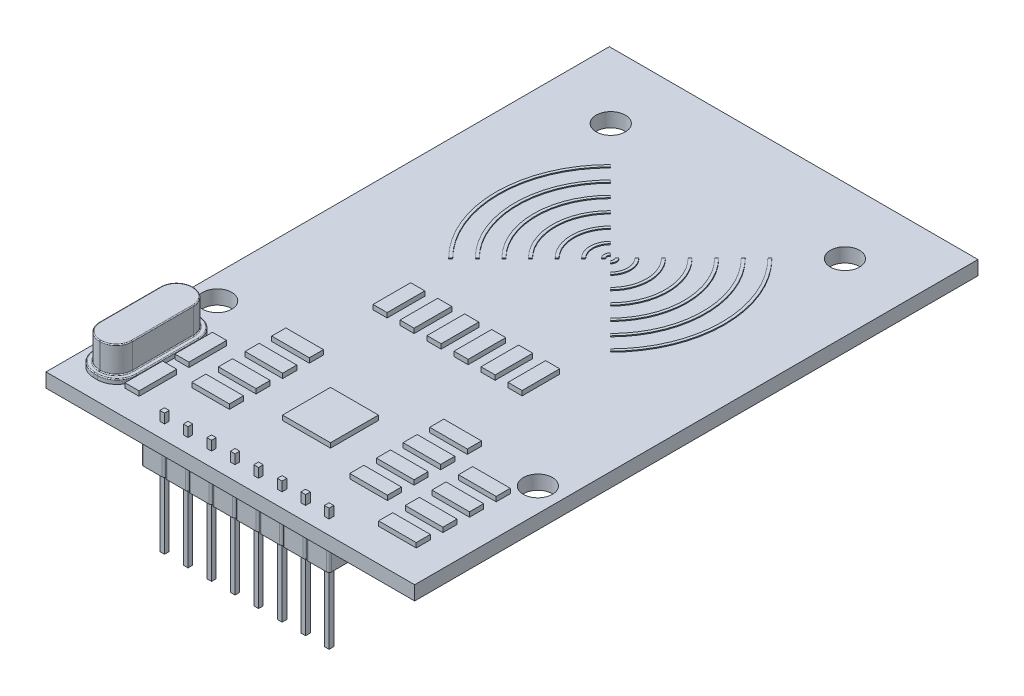
SolidWorks part; units mm, degrees
ref_plane "Front Plane" through (0, 0, 0) normal (0, 0, 1) x (1, 0, 0)
ref_plane "Top Plane" through (0, 0, 0) normal (0, 1, 0) x (1, 0, 0)
ref_plane "Right Plane" through (0, 0, 0) normal (1, 0, 0) x (0, 0, -1)
sketch "Sketch1" plane through (0, 0, 0) normal (0, 1, 0) x (1, 0, 0)
  line L1 (-19.6, 29.95) -> (19.6, 29.95)
  line L2 (-19.6, 29.95) -> (-19.6, -29.95)
  line L3 (-19.6, -29.95) -> (19.6, -29.95)
  line L4 (19.6, 29.95) -> (19.6, -29.95)
  line L5 (-19.6, 29.95) -> (19.6, -29.95) construction
  line L6 (-19.6, -29.95) -> (19.6, 29.95) construction
  point P0 (0, 0)
  dimension "D1" = 39.2
  dimension "D2" = 59.9
extrude "Boss-Extrude1" add sketch "Sketch1" along normal blind 1.5
sketch "Sketch3" plane through (0, 1.5, 0) normal (0, 1, 0) x (1, 0, 0)
  line L0 (0, 29.95) -> (0, -29.95) construction
  line L2 (19.6, 29.95) -> (-19.6, 29.95) construction
  line L3 (-17.05, -14.3) -> (17.05, -14.3) construction
  line L4 (-12.45, 22.95) -> (12.45, 22.95) construction
  line L5 (-19.6, -29.95) -> (19.6, -29.95) construction
  circle A0 centre (12.45, 22.95) radius 1.55
  circle A1 centre (-12.45, 22.95) radius 1.55
  circle A2 centre (17.05, -14.3) radius 1.55
  circle A3 centre (-17.05, -14.3) radius 1.55
  point P16 (0, 22.95)
  point P17 (0, -14.3)
  dimension "D1" = 3.1
  dimension "D2" = 12.45
  dimension "D3" = 7
  dimension "D6" = 17.05
  dimension "D7" = 15.65
extrude "Cut-Extrude1" cut sketch "Sketch3" against normal up to surface (1.5 mm away) up to face at (0, 0, 0)
sketch "Sketch4" plane through (0, 1.5, 0) normal (0, 1, 0) x (1, 0, 0)
  line L0 (-19.6, -29.95) -> (19.6, -29.95) construction
  line L1 (-9.75, -26.95) -> (-7.75, -26.95)
  line L2 (-10, -27.2) -> (-10, -29.2)
  line L3 (-9.75, -29.45) -> (-7.75, -29.45)
  line L5 (-19.6, 29.95) -> (-19.6, -29.95) construction
  line L7 (-7.25, -29.45) -> (-5.25, -29.45)
  line L9 (-7.25, -26.95) -> (-5.25, -26.95)
  line L11 (-4.75, -29.45) -> (-2.75, -29.45)
  line L13 (-4.75, -26.95) -> (-2.75, -26.95)
  line L15 (-2.25, -29.45) -> (-0.25, -29.45)
  line L17 (-2.25, -26.95) -> (-0.25, -26.95)
  line L19 (0.25, -29.45) -> (2.25, -29.45)
  line L21 (0.25, -26.95) -> (2.25, -26.95)
  line L23 (2.75, -29.45) -> (4.75, -29.45)
  line L25 (2.75, -26.95) -> (4.75, -26.95)
  line L27 (5.25, -29.45) -> (7.25, -29.45)
  line L29 (5.25, -26.95) -> (7.25, -26.95)
  line L30 (10, -27.2) -> (10, -29.2)
  line L31 (7.75, -29.45) -> (9.75, -29.45)
  line L33 (7.75, -26.95) -> (9.75, -26.95)
  line L34 (-7.5, -27.2) -> (-7.5, -29.2) [skipped]
  line L35 (-5, -27.2) -> (-5, -29.2) [skipped]
  line L36 (-2.5, -27.2) -> (-2.5, -29.2) [skipped]
  line L37 (0, -27.2) -> (0, -29.2) [skipped]
  line L38 (2.5, -27.2) -> (2.5, -29.2) [skipped]
  line L39 (5, -27.2) -> (5, -29.2) [skipped]
  line L40 (7.5, -27.2) -> (7.5, -29.2) [skipped]
  arc A1 (-7.75, -26.95) -> (-7.5, -27.2) centre (-7.75, -27.2) cw
  arc A2 (-7.5, -29.2) -> (-7.75, -29.45) centre (-7.75, -29.2) cw
  arc A3 (-9.75, -29.45) -> (-10, -29.2) centre (-9.75, -29.2) cw
  arc A4 (-10, -27.2) -> (-9.75, -26.95) centre (-9.75, -27.2) cw
  arc A5 (-5, -29.2) -> (-5.25, -29.45) centre (-5.25, -29.2) cw
  arc A6 (-7.25, -29.45) -> (-7.5, -29.2) centre (-7.25, -29.2) cw
  arc A7 (-7.5, -27.2) -> (-7.25, -26.95) centre (-7.25, -27.2) cw
  arc A8 (-5.25, -26.95) -> (-5, -27.2) centre (-5.25, -27.2) cw
  arc A10 (-2.5, -29.2) -> (-2.75, -29.45) centre (-2.75, -29.2) cw
  arc A11 (-4.75, -29.45) -> (-5, -29.2) centre (-4.75, -29.2) cw
  arc A12 (-5, -27.2) -> (-4.75, -26.95) centre (-4.75, -27.2) cw
  arc A13 (-2.75, -26.95) -> (-2.5, -27.2) centre (-2.75, -27.2) cw
  arc A15 (0, -29.2) -> (-0.25, -29.45) centre (-0.25, -29.2) cw
  arc A16 (-2.25, -29.45) -> (-2.5, -29.2) centre (-2.25, -29.2) cw
  arc A17 (-2.5, -27.2) -> (-2.25, -26.95) centre (-2.25, -27.2) cw
  arc A18 (-0.25, -26.95) -> (0, -27.2) centre (-0.25, -27.2) cw
  arc A20 (2.5, -29.2) -> (2.25, -29.45) centre (2.25, -29.2) cw
  arc A21 (0.25, -29.45) -> (0, -29.2) centre (0.25, -29.2) cw
  arc A22 (0, -27.2) -> (0.25, -26.95) centre (0.25, -27.2) cw
  arc A23 (2.25, -26.95) -> (2.5, -27.2) centre (2.25, -27.2) cw
  arc A25 (5, -29.2) -> (4.75, -29.45) centre (4.75, -29.2) cw
  arc A26 (2.75, -29.45) -> (2.5, -29.2) centre (2.75, -29.2) cw
  arc A27 (2.5, -27.2) -> (2.75, -26.95) centre (2.75, -27.2) cw
  arc A28 (4.75, -26.95) -> (5, -27.2) centre (4.75, -27.2) cw
  arc A30 (7.5, -29.2) -> (7.25, -29.45) centre (7.25, -29.2) cw
  arc A31 (5.25, -29.45) -> (5, -29.2) centre (5.25, -29.2) cw
  arc A32 (5, -27.2) -> (5.25, -26.95) centre (5.25, -27.2) cw
  arc A33 (7.25, -26.95) -> (7.5, -27.2) centre (7.25, -27.2) cw
  arc A35 (10, -29.2) -> (9.75, -29.45) centre (9.75, -29.2) cw
  arc A36 (7.75, -29.45) -> (7.5, -29.2) centre (7.75, -29.2) cw
  arc A37 (7.5, -27.2) -> (7.75, -26.95) centre (7.75, -27.2) cw
  arc A38 (9.75, -26.95) -> (10, -27.2) centre (9.75, -27.2) cw
  point P12 (-7.5, -26.95)
  point P17 (-10, -29.45)
  point P20 (-10, -26.95)
  dimension "D7" = 0.25
  dimension "D1" = 2.5
  dimension "D2" = 2.5
  dimension "D3" = 0.5
  dimension "D4" = 9.6
  dimension "D8" = 8
extrude "Boss-Extrude3" add sketch "Sketch4" against normal blind 4
ref_plane "Plane1" through (0, -1, 0) normal (0, -1, 0) x (-1, 0, 0)
sketch "Sketch8" plane through (0, 1.5, 0) normal (0, 1, 0) x (1, 0, 0)
  line L0 (-19.6, -29.95) -> (19.6, -29.95) construction
  line L1 (-16.5, -17.15) -> (-16.15, -17.15)
  line L2 (-18.6, -19.25) -> (-18.6, -25.85)
  line L3 (-16.5, -27.95) -> (-16.15, -27.95)
  line L4 (-14.05, -19.25) -> (-14.05, -25.85)
  line L6 (-19.6, 29.95) -> (-19.6, -29.95) construction
  arc A0 (-18.6, -25.85) -> (-16.5, -27.95) centre (-16.5, -25.85) ccw
  arc A1 (-16.15, -27.95) -> (-14.05, -25.85) centre (-16.15, -25.85) ccw
  arc A2 (-16.15, -17.15) -> (-14.05, -19.25) centre (-16.15, -19.25) cw
  arc A3 (-16.5, -17.15) -> (-18.6, -19.25) centre (-16.5, -19.25) ccw
  point P6 (-18.6, -27.95)
  point P11 (-14.05, -17.15)
  point P14 (-18.6, -17.15)
  dimension "D3" = 2.1
  dimension "D1" = 10.8
  dimension "D2" = 4.55
  dimension "D4" = 1
  dimension "D5" = 2
extrude "Boss-Extrude4" add sketch "Sketch8" along normal blind 0.5
sketch "Sketch10" plane through (0, 2, 0) normal (0, 1, 0) x (1, 0, 0)
  line L0 (-16.325, -17.15) -> (-16.325, -27.95) construction
  line L1 (-16.15, -17.15) -> (-16.5, -17.15) construction
  line L2 (-16.5, -27.95) -> (-16.15, -27.95) construction
  line L3 (-18.6, -22.55) -> (-14.05, -22.55) construction
  line L4 (-18.6, -19.25) -> (-18.6, -25.85) construction
  line L5 (-14.05, -25.85) -> (-14.05, -19.25) construction
  line L7 (-16.375, -17.6) -> (-16.275, -17.6)
  line L8 (-18.075, -19.3) -> (-18.075, -25.8)
  line L9 (-16.375, -27.5) -> (-16.275, -27.5)
  line L10 (-14.575, -19.3) -> (-14.575, -25.8)
  line L11 (-18.075, -17.6) -> (-14.575, -27.5) construction
  line L12 (-18.075, -27.5) -> (-14.575, -17.6) construction
  arc A0 (-18.075, -25.8) -> (-16.375, -27.5) centre (-16.375, -25.8) ccw
  arc A1 (-16.275, -27.5) -> (-14.575, -25.8) centre (-16.275, -25.8) ccw
  arc A2 (-14.575, -19.3) -> (-16.275, -17.6) centre (-16.275, -19.3) ccw
  arc A3 (-16.375, -17.6) -> (-18.075, -19.3) centre (-16.375, -19.3) ccw
  point P12 (-16.325, -22.55)
  dimension "D3" = 1.7
  dimension "D1" = 3.5
  dimension "D2" = 9.9
extrude "Boss-Extrude5" add sketch "Sketch10" along normal blind 2.8
fillet "Fillet1" radius 0.1 24 edges at (-17.5771, 4.8, 18.0979) (-16.325, 4.8, 17.6) (-15.0729, 4.8, 18.0979) (-14.575, 4.8, 22.55) (-15.0729, 4.8, 27.0021) (-16.325, 4.8, 27.5) (-17.5771, 4.8, 27.0021) (-17.5771, 2, 18.0979) (-16.325, 2, 17.6) (-15.0729, 2, 18.0979) (-14.575, 2, 22.55) (-15.0729, 2, 27.0021) (-16.325, 2, 27.5) (-17.5771, 2, 27.0021) (-17.9849, 2, 17.7651) (-16.325, 2, 17.15) (-14.6651, 2, 17.7651) (-14.05, 2, 22.55) (-14.6651, 2, 27.3349) (-16.325, 2, 27.95) (-17.9849, 2, 27.3349) (-18.075, 4.8, 22.55) (-18.075, 2, 22.55) (-18.6, 2, 22.55)
sketch "Sketch11" plane through (0, 1.5, 0) normal (0, 1, 0) x (1, 0, 0)
  line L0 (-0.2475, 10.6975) -> (-0.4596, 10.9096)
  line L1 (-0.35, 10.45) -> (-19.6, 10.45) construction
  line L2 (-19.6, 29.95) -> (-19.6, -29.95) construction
  line L3 (19.6, 29.95) -> (-19.6, 29.95) construction
  line L4 (0.2475, 10.6975) -> (0.4596, 10.9096)
  line L5 (-0.2475, 10.2025) -> (-0.4596, 9.9904)
  line L6 (0.2475, 10.2025) -> (0.4596, 9.9904)
  line L7 (-8.4853, 18.9353) -> (-8.5913, 19.0413)
  line L8 (-8.5913, 1.8587) -> (-8.4853, 1.9647)
  line L9 (8.4853, 1.9647) -> (8.5913, 1.8587)
  line L10 (8.4853, 18.9353) -> (8.5913, 19.0413)
  line L11 (-8.3792, 18.8292) -> (-8.4853, 18.9353)
  line L12 (-6.965, 17.415) -> (-7.1771, 17.6271)
  line L13 (-5.5508, 16.0008) -> (-5.7629, 16.2129)
  line L14 (-4.1366, 14.5866) -> (-4.3487, 14.7987)
  line L15 (-2.7224, 13.1724) -> (-2.9345, 13.3845)
  line L16 (-1.3081, 11.7581) -> (-1.5203, 11.9703)
  line L17 (-1.3081, 9.1419) -> (-1.5203, 8.9297)
  line L18 (-2.7224, 7.7276) -> (-2.9345, 7.5155)
  line L19 (-4.1366, 6.3134) -> (-4.3487, 6.1013)
  line L20 (-5.5508, 4.8992) -> (-5.7629, 4.6871)
  line L21 (-8.3792, 2.0708) -> (-8.4853, 1.9647)
  line L22 (1.3081, 9.1419) -> (1.5203, 8.9297)
  line L23 (2.7224, 7.7276) -> (2.9345, 7.5155)
  line L24 (4.1366, 6.3134) -> (4.3487, 6.1013)
  line L25 (5.5508, 4.8992) -> (5.7629, 4.6871)
  line L26 (6.965, 3.485) -> (7.1771, 3.2729)
  line L27 (8.3792, 2.0708) -> (8.4853, 1.9647)
  line L28 (1.3081, 11.7581) -> (1.5203, 11.9703)
  line L29 (2.7224, 13.1724) -> (2.9345, 13.3845)
  line L30 (4.1366, 14.5866) -> (4.3487, 14.7987)
  line L31 (5.5508, 16.0008) -> (5.7629, 16.2129)
  line L32 (6.965, 17.415) -> (7.1771, 17.6271)
  line L33 (8.3792, 18.8292) -> (8.4853, 18.9353)
  line L34 (-6.965, 3.485) -> (-7.1771, 3.2729)
  line L35 (0, 10.45) -> (0, 29.95) construction
  arc A0 (-0.3536, 10.8036) -> (-0.3536, 10.0964) centre (0, 10.45) ccw construction
  arc A1 (-1.4142, 11.8642) -> (-1.4142, 9.0358) centre (0, 10.45) ccw construction
  arc A2 (-2.8284, 13.2784) -> (-2.8284, 7.6216) centre (0, 10.45) ccw construction
  arc A3 (-4.2426, 14.6926) -> (-4.2426, 6.2074) centre (0, 10.45) ccw construction
  arc A4 (-5.6569, 16.1069) -> (-5.6569, 4.7931) centre (0, 10.45) ccw construction
  arc A5 (-5.6569, 16.1069) -> (-5.6569, 4.7931) centre (0, 10.45) ccw
  arc A6 (-7.0711, 17.5211) -> (-7.0711, 3.3789) centre (0, 10.45) ccw construction
  arc A7 (-8.4853, 18.9353) -> (-8.4853, 1.9647) centre (0, 10.45) ccw construction
  arc A8 (0.3536, 10.0964) -> (0.3536, 10.8036) centre (0, 10.45) ccw construction
  arc A9 (1.4142, 9.0358) -> (1.4142, 11.8642) centre (0, 10.45) ccw construction
  arc A10 (2.8284, 7.6216) -> (2.8284, 13.2784) centre (0, 10.45) ccw construction
  arc A11 (4.2426, 6.2074) -> (4.2426, 14.6926) centre (0, 10.45) ccw construction
  arc A12 (5.6569, 4.7931) -> (5.6569, 16.1069) centre (0, 10.45) ccw construction
  arc A13 (5.6569, 4.7931) -> (5.6569, 16.1069) centre (0, 10.45) ccw
  arc A14 (7.0711, 3.3789) -> (7.0711, 17.5211) centre (0, 10.45) ccw construction
  arc A15 (8.4853, 1.9647) -> (8.4853, 18.9353) centre (0, 10.45) ccw construction
  arc A16 (-8.5913, 19.0413) -> (-8.5913, 1.8587) centre (0, 10.45) ccw
  arc A17 (-7.1771, 17.6271) -> (-7.1771, 3.2729) centre (0, 10.45) ccw
  arc A18 (-5.7629, 16.2129) -> (-5.7629, 4.6871) centre (0, 10.45) ccw
  arc A19 (-4.3487, 14.7987) -> (-4.3487, 6.1013) centre (0, 10.45) ccw
  arc A20 (-2.9345, 13.3845) -> (-2.9345, 7.5155) centre (0, 10.45) ccw
  arc A21 (-1.5203, 11.9703) -> (-1.5203, 8.9297) centre (0, 10.45) ccw
  arc A22 (-0.4596, 10.9096) -> (-0.4596, 9.9904) centre (0, 10.45) ccw
  arc A23 (0.4596, 9.9904) -> (0.4596, 10.9096) centre (0, 10.45) ccw
  arc A24 (1.5203, 8.9297) -> (1.5203, 11.9703) centre (0, 10.45) ccw
  arc A25 (2.9345, 7.5155) -> (2.9345, 13.3845) centre (0, 10.45) ccw
  arc A26 (4.3487, 6.1013) -> (4.3487, 14.7987) centre (0, 10.45) ccw
  arc A27 (5.7629, 4.6871) -> (5.7629, 16.2129) centre (0, 10.45) ccw
  arc A28 (7.1771, 3.2729) -> (7.1771, 17.6271) centre (0, 10.45) ccw
  arc A29 (8.5913, 1.8587) -> (8.5913, 19.0413) centre (0, 10.45) ccw
  arc A30 (-8.3792, 18.8292) -> (-8.3792, 2.0708) centre (0, 10.45) ccw
  arc A31 (-6.965, 17.415) -> (-6.965, 3.485) centre (0, 10.45) ccw
  arc A32 (-5.5508, 16.0008) -> (-5.5508, 4.8992) centre (0, 10.45) ccw
  arc A33 (-4.1366, 14.5866) -> (-4.1366, 6.3134) centre (0, 10.45) ccw
  arc A34 (-2.7224, 13.1724) -> (-2.7224, 7.7276) centre (0, 10.45) ccw
  arc A35 (-1.3081, 11.7581) -> (-1.3081, 9.1419) centre (0, 10.45) ccw
  arc A36 (-0.2475, 10.6975) -> (-0.2475, 10.2025) centre (0, 10.45) ccw
  arc A37 (0.2475, 10.2025) -> (0.2475, 10.6975) centre (0, 10.45) ccw
  arc A38 (1.3081, 9.1419) -> (1.3081, 11.7581) centre (0, 10.45) ccw
  arc A39 (2.7224, 7.7276) -> (2.7224, 13.1724) centre (0, 10.45) ccw
  arc A40 (4.1366, 6.3134) -> (4.1366, 14.5866) centre (0, 10.45) ccw
  arc A41 (5.5508, 4.8992) -> (5.5508, 16.0008) centre (0, 10.45) ccw
  arc A42 (6.965, 3.485) -> (6.965, 17.415) centre (0, 10.45) ccw
  arc A43 (8.3792, 2.0708) -> (8.3792, 18.8292) centre (0, 10.45) ccw
  dimension "D1" = 45
  dimension "D2" = 0.5
  dimension "D3" = 2
  dimension "D4" = 6
  dimension "D5" = 10
  dimension "D6" = 19.5
  dimension "D10" = 8
  dimension "D11" = 4
  dimension "D12" = 12
  dimension "D7" = 45
  dimension "D8" = 45
  dimension "D9" = 45
  dimension "D13" = 0.15
  dimension "D14" = 0.15
extrude "Boss-Extrude6" add sketch "Sketch11" along normal blind 0.1 contours A16 L8 L21 A30 L11 L7 | A17 L34 A31 L12 | A18 L20 A32 L13 | A19 L19 A33 L14 | A20 L18 A34 L15 | A35 L17 A21 L16 | A36 L5 A22 L0 | A23 L4 A37 L6 | A24 L28 A38 L22 | A25 L29 A39 L23 | A26 L30 A40 L24 | A27 L31 A41 L25 | A28 L32 A42 L26 | A29 L10 L33 A43 L27 L9
sketch "Esboço1" plane through (0, 1.5, 0) normal (0, 1, 0) x (1, 0, 0)
  line L0 (6.425, -4.85) -> (5.055, -4.85) construction
  line L1 (6.425, -2.85) -> (7.925, -2.85)
  line L2 (6.425, -2.85) -> (6.425, -6.85)
  line L3 (6.425, -6.85) -> (7.925, -6.85)
  line L4 (7.925, -2.85) -> (7.925, -6.85)
  line L5 (3.555, -4.85) -> (2.185, -4.85) construction
  line L6 (5.055, -2.85) -> (3.555, -2.85)
  line L7 (5.055, -2.85) -> (5.055, -6.85)
  line L8 (5.055, -6.85) -> (3.555, -6.85)
  line L9 (3.555, -2.85) -> (3.555, -6.85)
  line L10 (2.185, -2.85) -> (0.685, -2.85)
  line L11 (2.185, -2.85) -> (2.185, -6.85)
  line L12 (2.185, -6.85) -> (0.685, -6.85)
  line L13 (0.685, -2.85) -> (0.685, -6.85)
  line L14 (-0.685, -2.85) -> (-2.185, -2.85)
  line L15 (-0.685, -2.85) -> (-0.685, -6.85)
  line L16 (-0.685, -6.85) -> (-2.185, -6.85)
  line L17 (-2.185, -2.85) -> (-2.185, -6.85)
  line L18 (-3.555, -2.85) -> (-5.055, -2.85)
  line L19 (-3.555, -2.85) -> (-3.555, -6.85)
  line L20 (-3.555, -6.85) -> (-5.055, -6.85)
  line L21 (-5.055, -2.85) -> (-5.055, -6.85)
  line L22 (-6.425, -2.85) -> (-7.925, -2.85)
  line L23 (-6.425, -2.85) -> (-6.425, -6.85)
  line L24 (-6.425, -6.85) -> (-7.925, -6.85)
  line L25 (-7.925, -2.85) -> (-7.925, -6.85)
  line L26 (-8.4, -22.15) -> (-8.4, -20.8167) construction
  line L27 (0.685, -4.85) -> (-0.685, -4.85) construction
  line L28 (-8.4, -19.3167) -> (-8.4, -17.9833) construction
  line L29 (-2.185, -4.85) -> (-3.555, -4.85) construction
  line L30 (-8.4, -16.4833) -> (-8.4, -15.15) construction
  line L31 (-5.055, -4.85) -> (-6.425, -4.85) construction
  line L32 (0, 0) -> (0, -18.65) construction
  line L33 (19.6, 29.95) -> (-19.6, 29.95) construction
  line L34 (8.4, -22.15) -> (8.4, -20.8167) construction
  line L35 (-10.4, -23.65) -> (-6.4, -23.65)
  line L36 (-10.4, -23.65) -> (-10.4, -22.15)
  line L37 (-10.4, -22.15) -> (-6.4, -22.15)
  line L38 (-6.4, -23.65) -> (-6.4, -22.15)
  line L39 (-10.4, -19.3167) -> (-6.4, -19.3167)
  line L40 (-10.4, -19.3167) -> (-10.4, -20.8167)
  line L41 (-10.4, -20.8167) -> (-6.4, -20.8167)
  line L42 (-6.4, -19.3167) -> (-6.4, -20.8167)
  line L43 (-10.4, -16.4833) -> (-6.4, -16.4833)
  line L44 (-10.4, -16.4833) -> (-10.4, -17.9833)
  line L45 (-10.4, -17.9833) -> (-6.4, -17.9833)
  line L46 (-6.4, -16.4833) -> (-6.4, -17.9833)
  line L47 (-10.4, -13.65) -> (-6.4, -13.65)
  line L48 (-10.4, -13.65) -> (-10.4, -15.15)
  line L49 (-10.4, -15.15) -> (-6.4, -15.15)
  line L50 (-6.4, -13.65) -> (-6.4, -15.15)
  line L51 (6.4, -13.65) -> (10.4, -13.65)
  line L52 (6.4, -13.65) -> (6.4, -15.15)
  line L53 (6.4, -15.15) -> (10.4, -15.15)
  line L54 (10.4, -13.65) -> (10.4, -15.15)
  line L55 (6.4, -16.4833) -> (10.4, -16.4833)
  line L56 (6.4, -16.4833) -> (6.4, -17.9833)
  line L57 (6.4, -17.9833) -> (10.4, -17.9833)
  line L58 (10.4, -16.4833) -> (10.4, -17.9833)
  line L59 (6.4, -19.3167) -> (10.4, -19.3167)
  line L60 (6.4, -19.3167) -> (6.4, -20.8167)
  line L61 (6.4, -20.8167) -> (10.4, -20.8167)
  line L62 (10.4, -19.3167) -> (10.4, -20.8167)
  line L63 (6.4, -22.15) -> (10.4, -22.15)
  line L64 (6.4, -22.15) -> (6.4, -23.65)
  line L65 (6.4, -23.65) -> (10.4, -23.65)
  line L66 (10.4, -22.15) -> (10.4, -23.65)
  line L67 (8.4, -19.3167) -> (8.4, -17.9833) construction
  line L68 (-8.4, -18.65) -> (8.4, -18.65) construction
  line L69 (8.4, -16.4833) -> (8.4, -15.15) construction
  line L70 (-19.6, 29.95) -> (-19.6, -29.95) construction
  line L71 (-13.15, -21.95) -> (-13.15, -23.25) construction
  line L72 (-13.9, -17.95) -> (-12.4, -17.95)
  line L73 (-13.9, -17.95) -> (-13.9, -21.95)
  line L74 (-13.9, -21.95) -> (-12.4, -21.95)
  line L75 (-12.4, -17.95) -> (-12.4, -21.95)
  line L76 (-13.9, -23.25) -> (-12.4, -23.25)
  line L77 (-13.9, -23.25) -> (-13.9, -27.25)
  line L78 (-13.9, -27.25) -> (-12.4, -27.25)
  line L79 (-12.4, -23.25) -> (-12.4, -27.25)
  line L80 (-19.6, -29.95) -> (19.6, -29.95) construction
  line L81 (14.3, -17.9833) -> (14.3, -19.3167) construction
  line L82 (12.3, -16.4833) -> (16.3, -16.4833)
  line L83 (12.3, -16.4833) -> (12.3, -17.9833)
  line L84 (12.3, -17.9833) -> (16.3, -17.9833)
  line L85 (16.3, -16.4833) -> (16.3, -17.9833)
  line L86 (12.3, -19.3167) -> (16.3, -19.3167)
  line L87 (12.3, -19.3167) -> (12.3, -20.8167)
  line L88 (12.3, -20.8167) -> (16.3, -20.8167)
  line L89 (16.3, -19.3167) -> (16.3, -20.8167)
  line L90 (12.3, -22.15) -> (16.3, -22.15)
  line L91 (12.3, -22.15) -> (12.3, -23.65)
  line L92 (12.3, -23.65) -> (16.3, -23.65)
  line L93 (16.3, -22.15) -> (16.3, -23.65)
  line L94 (12.3, -24.9833) -> (16.3, -24.9833)
  line L95 (12.3, -24.9833) -> (12.3, -26.4833)
  line L96 (12.3, -26.4833) -> (16.3, -26.4833)
  line L97 (16.3, -24.9833) -> (16.3, -26.4833)
  line L98 (14.3, -20.8167) -> (14.3, -22.15) construction
  line L99 (14.3, -23.65) -> (14.3, -24.9833) construction
  line L100 (19.6, -29.95) -> (19.6, 29.95) construction
  point P34 (0, -4.85)
  point P86 (0, -18.65)
  dimension "D1" = 1.5
  dimension "D2" = 4
  dimension "D3" = 1.37
  dimension "D4" = 32.8
  dimension "D5" = 43.6
  dimension "D6" = 10
  dimension "D7" = 9.2
  dimension "D8" = 9.3
  dimension "D9" = 7.2
  dimension "D10" = 12
  dimension "D11" = 3.3
extrude "Ressalto-extrusão1" add sketch "Esboço1" along normal blind 0.5
sketch "Esboço2" plane through (0, 1.5, 0) normal (0, 1, 0) x (1, 0, 0)
  line L0 (0, 0) -> (0, -16.75) construction
  line L1 (-2.55, -16.75) -> (2.55, -16.75)
  line L2 (-2.55, -16.75) -> (-2.55, -21.85)
  line L3 (-2.55, -21.85) -> (2.55, -21.85)
  line L4 (2.55, -16.75) -> (2.55, -21.85)
  line L5 (19.6, 29.95) -> (-19.6, 29.95) construction
  dimension "D1" = 5.1
  dimension "D2" = 46.7
extrude "Ressalto-extrusão2" add sketch "Esboço2" along normal blind 0.5
sketch "Sketch12" plane through (0, -2.5, 0) normal (0, -1, 0) x (1, 0, 0)
  line L1 (6, 28.45) -> (6, 27.95)
  line L2 (6, 28.45) -> (6.5, 28.45)
  line L4 (6.5, 28.45) -> (6.5, 27.95)
  line L7 (6, 27.95) -> (6.5, 27.95)
  line L8 (8.5, 28.45) -> (9, 28.45)
  line L9 (8.5, 28.45) -> (8.5, 27.95)
  line L10 (8.5, 27.95) -> (9, 27.95)
  line L11 (9, 28.45) -> (9, 27.95)
  line L12 (8.5, 28.45) -> (9, 27.95) construction
  line L13 (8.5, 27.95) -> (9, 28.45) construction
  line L14 (3.5, 28.45) -> (3.5, 27.95)
  line L15 (3.5, 28.45) -> (4, 28.45)
  line L16 (4, 28.45) -> (4, 27.95)
  line L17 (3.5, 27.95) -> (4, 27.95)
  line L18 (1, 28.45) -> (1, 27.95)
  line L19 (1, 28.45) -> (1.5, 28.45)
  line L20 (1.5, 28.45) -> (1.5, 27.95)
  line L21 (1, 27.95) -> (1.5, 27.95)
  line L22 (-1.5, 28.45) -> (-1.5, 27.95)
  line L23 (-1.5, 28.45) -> (-1, 28.45)
  line L24 (-1, 28.45) -> (-1, 27.95)
  line L25 (-1.5, 27.95) -> (-1, 27.95)
  line L26 (-4, 28.45) -> (-4, 27.95)
  line L27 (-4, 28.45) -> (-3.5, 28.45)
  line L28 (-3.5, 28.45) -> (-3.5, 27.95)
  line L29 (-4, 27.95) -> (-3.5, 27.95)
  line L30 (-6.5, 28.45) -> (-6.5, 27.95)
  line L31 (-6.5, 28.45) -> (-6, 28.45)
  line L32 (-6, 28.45) -> (-6, 27.95)
  line L33 (-6.5, 27.95) -> (-6, 27.95)
  line L34 (-9, 28.45) -> (-9, 27.95)
  line L35 (-9, 28.45) -> (-8.5, 28.45)
  line L36 (-8.5, 28.45) -> (-8.5, 27.95)
  line L37 (-9, 27.95) -> (-8.5, 27.95)
  point P6 (8.75, 28.2)
  dimension "D1" = 8
extrude "Cut-Extrude2" cut sketch "Sketch12" against normal blind 10 and the other way blind 10
sketch "Sketch13" plane through (0, -2.5, 0) normal (0, -1, 0) x (1, 0, 0)
  line L0 (6.5, 28.45) -> (6.5, 27.95) construction
  line L1 (6, 28.45) -> (6.5, 28.45) construction
  line L2 (6, 27.95) -> (6, 28.45) construction
  line L3 (6.5, 27.95) -> (6, 27.95) construction
  line L4 (6.5, 28.45) -> (6.5, 27.95)
  line L5 (6, 28.45) -> (6.5, 28.45)
  line L6 (6, 27.95) -> (6, 28.45)
  line L7 (6.5, 27.95) -> (6, 27.95)
  line L8 (8.5, 28.45) -> (8.5, 27.95) construction
  line L9 (8.5, 28.45) -> (9, 28.45) construction
  line L10 (9, 28.45) -> (9, 27.95) construction
  line L11 (8.5, 27.95) -> (9, 27.95) construction
  line L12 (8.5, 28.45) -> (8.5, 27.95)
  line L13 (8.5, 28.45) -> (9, 28.45)
  line L14 (9, 28.45) -> (9, 27.95)
  line L15 (8.5, 27.95) -> (9, 27.95)
  line L16 (3.5, 28.45) -> (4, 28.45) construction
  line L17 (4, 28.45) -> (4, 27.95) construction
  line L18 (3.5, 27.95) -> (4, 27.95) construction
  line L19 (3.5, 28.45) -> (3.5, 27.95) construction
  line L20 (-1, 28.45) -> (-1, 27.95) construction
  line L21 (-1.5, 28.45) -> (-1, 28.45) construction
  line L22 (-1.5, 27.95) -> (-1, 27.95) construction
  line L23 (-1.5, 28.45) -> (-1.5, 27.95) construction
  line L24 (1, 28.45) -> (1, 27.95) construction
  line L25 (1, 27.95) -> (1.5, 27.95) construction
  line L26 (1.5, 28.45) -> (1.5, 27.95) construction
  line L27 (1, 28.45) -> (1.5, 28.45) construction
  line L28 (-3.5, 28.45) -> (-3.5, 27.95) construction
  line L29 (-4, 27.95) -> (-3.5, 27.95) construction
  line L30 (-4, 28.45) -> (-3.5, 28.45) construction
  line L31 (-4, 28.45) -> (-4, 27.95) construction
  line L32 (-6.5, 28.45) -> (-6.5, 27.95) construction
  line L33 (-6.5, 27.95) -> (-6, 27.95) construction
  line L34 (-6, 28.45) -> (-6, 27.95) construction
  line L35 (-6.5, 28.45) -> (-6, 28.45) construction
  line L36 (-8.5, 28.45) -> (-8.5, 27.95) construction
  line L37 (-9, 27.95) -> (-8.5, 27.95) construction
  line L38 (-9, 28.45) -> (-8.5, 28.45) construction
  line L39 (-9, 28.45) -> (-9, 27.95) construction
  line L40 (-9, 28.45) -> (-9, 27.95)
  line L41 (-9, 28.45) -> (-8.5, 28.45)
  line L42 (-9, 27.95) -> (-8.5, 27.95)
  line L43 (-8.5, 28.45) -> (-8.5, 27.95)
  line L44 (-6.5, 28.45) -> (-6, 28.45)
  line L45 (-6, 28.45) -> (-6, 27.95)
  line L46 (-6.5, 27.95) -> (-6, 27.95)
  line L47 (-6.5, 28.45) -> (-6.5, 27.95)
  line L48 (-4, 28.45) -> (-4, 27.95)
  line L49 (-4, 28.45) -> (-3.5, 28.45)
  line L50 (-4, 27.95) -> (-3.5, 27.95)
  line L51 (-3.5, 28.45) -> (-3.5, 27.95)
  line L52 (1, 28.45) -> (1.5, 28.45)
  line L53 (1.5, 28.45) -> (1.5, 27.95)
  line L54 (1, 27.95) -> (1.5, 27.95)
  line L55 (1, 28.45) -> (1, 27.95)
  line L56 (-1.5, 28.45) -> (-1.5, 27.95)
  line L57 (-1.5, 27.95) -> (-1, 27.95)
  line L58 (-1.5, 28.45) -> (-1, 28.45)
  line L59 (-1, 28.45) -> (-1, 27.95)
  line L60 (3.5, 28.45) -> (3.5, 27.95)
  line L61 (3.5, 27.95) -> (4, 27.95)
  line L62 (4, 28.45) -> (4, 27.95)
  line L63 (3.5, 28.45) -> (4, 28.45)
extrude "Boss-Extrude8" add sketch "Sketch13" along normal blind 8 and the other way blind 5
